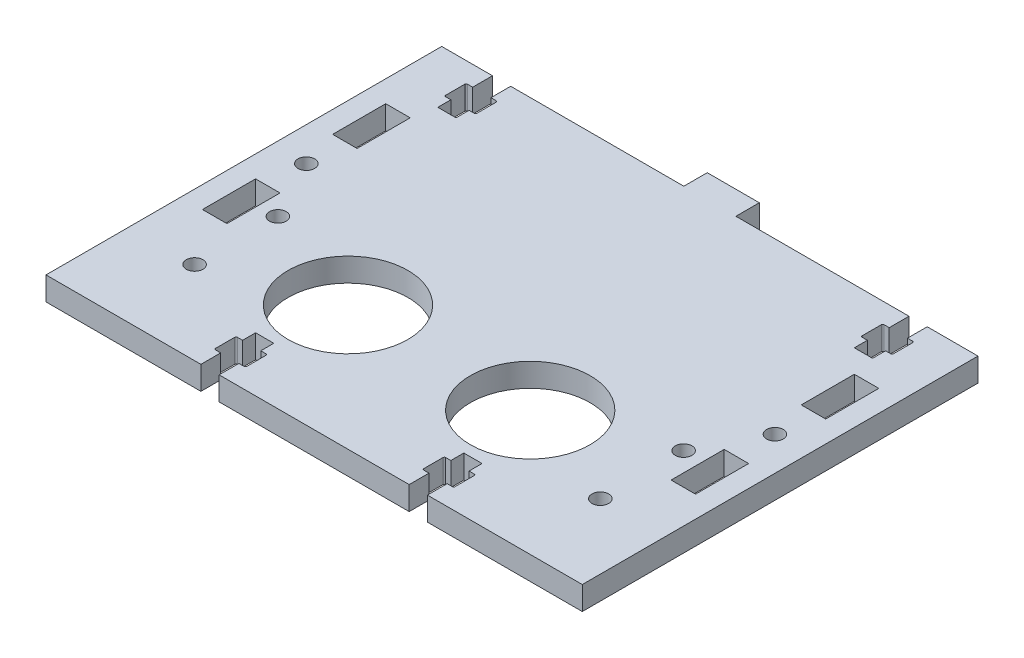
SolidWorks part; units mm, degrees
ref_plane "Front Plane" through (0, 0, 0) normal (0, 0, 1) x (1, 0, 0)
ref_plane "Top Plane" through (0, 0, 0) normal (0, 1, 0) x (1, 0, 0)
ref_plane "Right Plane" through (0, 0, 0) normal (1, 0, 0) x (0, 0, -1)
sketch "Sketch1" plane through (0, 0, 0) normal (0, 1, 0) x (1, 0, 0)
  line L1 (-51.5, 38) -> (51.5, 38)
  line L2 (-51.5, 38) -> (-51.5, -38)
  line L3 (-51.5, -38) -> (51.5, -38)
  line L4 (51.5, 38) -> (51.5, -38)
  line L5 (-51.5, 38) -> (51.5, -38) construction
  line L6 (-51.5, -38) -> (51.5, 38) construction
  point P0 (0, 0)
  dimension "D1" = 103
  dimension "D2" = 76
extrude "MainShape" add sketch "Sketch1" along normal blind 4.5
sketch "Sketch2" plane through (0, 4.5, 0) normal (0, 1, 0) x (1, 0, 0)
  line L0 (0, -38) -> (0, 38) construction
  line L1 (-51.5, -38) -> (51.5, -38) construction
  line L2 (51.5, 38) -> (-51.5, 38) construction
  line L4 (-5, 42.5) -> (5, 42.5)
  line L5 (-5, 42.5) -> (-5, 33.5)
  line L6 (-5, 33.5) -> (5, 33.5)
  line L7 (5, 42.5) -> (5, 33.5)
  line L8 (-5, 42.5) -> (5, 33.5) construction
  line L9 (-5, 33.5) -> (5, 42.5) construction
  dimension "D2" = 4.5
extrude "Tab1" add sketch "Sketch2" against normal through all
sketch "Sketch4" plane through (0, 4.5, 0) normal (0, 1, 0) x (1, 0, 0)
  line L0 (0, 42.5) -> (0, -38) construction
  line L1 (5, 42.5) -> (-5, 42.5) construction
  line L2 (-51.5, -38) -> (51.5, -38) construction
  line L3 (-40, 38) -> (-40, 27.5) construction
  line L4 (-5, 38) -> (-51.5, 38) construction
  line L5 (-38.25, 27.5) -> (-41.75, 27.5) construction
  line L6 (-41.75, 27.5) -> (-41.75, 38) construction
  line L7 (-38.25, 27.5) -> (-41.75, 27.5)
  line L8 (-41.75, 27.5) -> (-41.75, 30)
  line L9 (-41.75, 30) -> (-42.75, 30)
  line L10 (-43, 30.25) -> (-43, 33.95)
  line L11 (-42.75, 34.2) -> (-41.75, 34.2)
  line L12 (-41.75, 34.2) -> (-41.75, 38)
  line L13 (-41.75, 38) -> (-38.25, 38)
  line L14 (-38.25, 27.5) -> (-38.25, 38) construction
  line L15 (-38.25, 34.2) -> (-38.25, 38)
  line L16 (-37.25, 34.2) -> (-38.25, 34.2)
  line L17 (-37, 30.25) -> (-37, 33.95)
  line L18 (-38.25, 30) -> (-37.25, 30)
  line L19 (-38.25, 27.5) -> (-38.25, 30)
  line L20 (38.25, 27.5) -> (38.25, 38) construction
  line L21 (41.75, 27.5) -> (41.75, 38) construction
  line L22 (38.25, 27.5) -> (41.75, 27.5) construction
  line L23 (40, 38) -> (40, 27.5) construction
  line L24 (38.25, 27.5) -> (38.25, 30)
  line L25 (38.25, 30) -> (37.25, 30)
  line L26 (37, 30.25) -> (37, 33.95)
  line L27 (37.25, 34.2) -> (38.25, 34.2)
  line L28 (38.25, 34.2) -> (38.25, 38)
  line L29 (41.75, 38) -> (38.25, 38)
  line L30 (41.75, 34.2) -> (41.75, 38)
  line L31 (42.75, 34.2) -> (41.75, 34.2)
  line L32 (43, 30.25) -> (43, 33.95)
  line L33 (41.75, 30) -> (42.75, 30)
  line L34 (41.75, 27.5) -> (41.75, 30)
  line L35 (38.25, 27.5) -> (41.75, 27.5)
  arc A0 (-42.75, 30) -> (-43, 30.25) centre (-42.75, 30.25) cw
  arc A1 (-37, 30.25) -> (-37.25, 30) centre (-37.25, 30.25) cw
  arc A2 (-37.25, 34.2) -> (-37, 33.95) centre (-37.25, 33.95) cw
  arc A3 (-43, 33.95) -> (-42.75, 34.2) centre (-42.75, 33.95) cw
  arc A4 (43, 33.95) -> (42.75, 34.2) centre (42.75, 33.95) ccw
  arc A5 (37.25, 34.2) -> (37, 33.95) centre (37.25, 33.95) ccw
  arc A6 (37, 30.25) -> (37.25, 30) centre (37.25, 30.25) ccw
  arc A7 (42.75, 30) -> (43, 30.25) centre (42.75, 30.25) ccw
  point P24 (-43, 30)
  point P27 (-37, 30)
  point P30 (-37, 34.2)
  point P33 (-43, 34.2)
  point P56 (43, 34.2)
  point P57 (37, 34.2)
  point P58 (37, 30)
  point P59 (43, 30)
  dimension "D7" = 0.25
  dimension "D1" = 10.5
  dimension "D2" = 1.75
  dimension "D3" = 4.2
  dimension "D4" = 3
  dimension "D5" = 8
  dimension "D6" = 40
extrude "Cut-Extrude2" cut sketch "Sketch4" against normal through all
sketch "Sketch5" plane through (0, 4.5, 0) normal (0, 1, 0) x (1, 0, 0)
  line L0 (0, -38) -> (0, 42.5) construction
  line L1 (-51.5, -38) -> (51.5, -38) construction
  line L2 (5, 42.5) -> (-5, 42.5) construction
  line L3 (45, 38) -> (45, -38) construction
  line L4 (51.5, 38) -> (41.75, 38) construction
  line L5 (-45, 38) -> (-45, -38) construction
  line L6 (42.65, 23.1) -> (47.35, 23.1)
  line L7 (42.65, 23.1) -> (42.65, 12.9)
  line L8 (42.65, 12.9) -> (47.35, 12.9)
  line L9 (47.35, 23.1) -> (47.35, 12.9)
  line L10 (42.65, 23.1) -> (47.35, 12.9) construction
  line L11 (42.65, 12.9) -> (47.35, 23.1) construction
  line L12 (-42.65, 12.9) -> (-47.35, 23.1) construction
  line L13 (-42.65, 23.1) -> (-47.35, 12.9) construction
  line L14 (-47.35, 23.1) -> (-47.35, 12.9)
  line L15 (-42.65, 12.9) -> (-47.35, 12.9)
  line L16 (-42.65, 23.1) -> (-42.65, 12.9)
  line L17 (-42.65, 23.1) -> (-47.35, 23.1)
  line L18 (-51.5, 5.5) -> (51.5, 5.5) construction
  line L19 (-51.5, 38) -> (-51.5, -38) construction
  line L20 (51.5, -38) -> (51.5, 38) construction
  line L21 (-42.65, -12.1) -> (-47.35, -1.9) construction
  line L22 (-42.65, -1.9) -> (-47.35, -12.1) construction
  line L23 (42.65, -1.9) -> (47.35, -12.1) construction
  line L24 (42.65, -12.1) -> (47.35, -1.9) construction
  line L25 (-42.65, -12.1) -> (-47.35, -12.1)
  line L26 (-42.65, -12.1) -> (-42.65, -1.9)
  line L27 (-42.65, -1.9) -> (-47.35, -1.9)
  line L28 (-47.35, -12.1) -> (-47.35, -1.9)
  line L29 (47.35, -12.1) -> (47.35, -1.9)
  line L30 (42.65, -1.9) -> (47.35, -1.9)
  line L31 (42.65, -12.1) -> (42.65, -1.9)
  line L32 (42.65, -12.1) -> (47.35, -12.1)
  line L33 (-42.65, 23.1) -> (-47.35, 12.9) construction
  circle A0 centre (45, 5.5) radius 1.6
  circle A1 centre (-45, 5.5) radius 1.6
  point P10 (45, 18)
  point P21 (-45, 18)
  point P36 (-45, -7)
  point P37 (45, -7)
  dimension "D6" = 3.2
  dimension "D1" = 45
  dimension "D2" = 10.2
  dimension "D3" = 4.7
  dimension "D4" = 20
  dimension "D5" = 25
extrude "Cut-Extrude3" cut sketch "Sketch5" against normal through all
sketch "Sketch6" plane through (0, 4.5, 0) normal (0, 1, 0) x (1, 0, 0)
  line L0 (-17.5, -28) -> (-17.5, 28) construction
  line L2 (5, 42.5) -> (-5, 42.5) construction
  line L3 (-51.5, -14) -> (51.5, -14) construction
  line L4 (-51.5, 38) -> (-51.5, -38) construction
  line L5 (51.5, -38) -> (51.5, 38) construction
  line L6 (51.5, 38) -> (41.75, 38) construction
  line L7 (-51.5, -38) -> (51.5, -38) construction
  line L9 (-51.5, 38) -> (51.5, 38) construction
  circle A0 centre (-17.5, -14) radius 11.5
  point P4 (0, 42.5)
  dimension "D1" = 23
  dimension "D2" = 52
  dimension "D4" = 17.5
extrude "Cut-Extrude4" cut sketch "Sketch6" against normal through all
sketch "Sketch8" plane through (0, 4.5, 0) normal (0, 1, 0) x (1, 0, 0)
  line L0 (-17.5, -2.5) -> (-17.5, -25.5) construction
  line L1 (-17.5, -14) -> (-38.96, -14) construction
  line L2 (-38.96, -22) -> (-38.96, -6) construction
  line L3 (-17.5, -25.5) -> (-17.5, -2.5) construction
  circle A0 centre (-38.96, -6) radius 1.6
  circle A1 centre (-17.5, -14) radius 11.5 construction
  circle A2 centre (-38.96, -22) radius 1.6
  dimension "D3" = 3.2
  dimension "D1" = 0
  dimension "D4" = 21.46
extrude "Cut-Extrude6" cut sketch "Sketch8" against normal through all
sketch "Sketch9" plane through (0, 4.5, 0) normal (0, 1, 0) x (1, 0, 0)
  line L0 (0, -38) -> (0, 42.5) construction
  line L1 (-51.5, -38) -> (51.5, -38) construction
  line L2 (5, 42.5) -> (-5, 42.5) construction
  line L3 (20, -38) -> (20, -27.5) construction
  line L4 (18.25, -27.5) -> (21.75, -27.5) construction
  line L5 (21.75, -27.5) -> (21.75, -38) construction
  line L6 (21.75, -38) -> (21.75, -34.2)
  line L7 (21.75, -34.2) -> (22.75, -34.2)
  line L8 (23, -33.95) -> (23, -30.25)
  line L9 (22.75, -30) -> (21.75, -30)
  line L10 (21.75, -30) -> (21.75, -27.5)
  line L11 (21.75, -27.5) -> (18.25, -27.5)
  line L12 (21.75, -38) -> (18.25, -38)
  line L13 (18.25, -27.5) -> (18.25, -38) construction
  line L14 (18.25, -30) -> (18.25, -27.5)
  line L15 (17.25, -30) -> (18.25, -30)
  line L16 (17, -33.95) -> (17, -30.25)
  line L17 (18.25, -34.2) -> (17.25, -34.2)
  line L18 (18.25, -38) -> (18.25, -34.2)
  line L19 (-18.25, -27.5) -> (-18.25, -38) construction
  line L20 (-21.75, -27.5) -> (-21.75, -38) construction
  line L21 (-18.25, -27.5) -> (-21.75, -27.5) construction
  line L22 (-20, -38) -> (-20, -27.5) construction
  line L23 (-18.25, -38) -> (-18.25, -34.2)
  line L24 (-18.25, -34.2) -> (-17.25, -34.2)
  line L25 (-17, -33.95) -> (-17, -30.25)
  line L26 (-17.25, -30) -> (-18.25, -30)
  line L27 (-18.25, -30) -> (-18.25, -27.5)
  line L28 (-21.75, -38) -> (-18.25, -38)
  line L29 (-21.75, -27.5) -> (-18.25, -27.5)
  line L30 (-21.75, -30) -> (-21.75, -27.5)
  line L31 (-22.75, -30) -> (-21.75, -30)
  line L32 (-23, -33.95) -> (-23, -30.25)
  line L33 (-21.75, -34.2) -> (-22.75, -34.2)
  line L34 (-21.75, -38) -> (-21.75, -34.2)
  arc A0 (22.75, -34.2) -> (23, -33.95) centre (22.75, -33.95) ccw
  arc A1 (23, -30.25) -> (22.75, -30) centre (22.75, -30.25) ccw
  arc A2 (17, -30.25) -> (17.25, -30) centre (17.25, -30.25) cw
  arc A3 (17.25, -34.2) -> (17, -33.95) centre (17.25, -33.95) cw
  arc A4 (-17.25, -34.2) -> (-17, -33.95) centre (-17.25, -33.95) ccw
  arc A5 (-17, -30.25) -> (-17.25, -30) centre (-17.25, -30.25) ccw
  arc A6 (-23, -30.25) -> (-22.75, -30) centre (-22.75, -30.25) cw
  arc A7 (-22.75, -34.2) -> (-23, -33.95) centre (-22.75, -33.95) cw
  point P16 (23, -34.2)
  point P19 (23, -30)
  point P30 (17, -30)
  point P31 (17, -34.2)
  point P54 (-17, -34.2)
  point P55 (-17, -30)
  point P56 (-23, -30)
  point P57 (-23, -34.2)
  dimension "D7" = 0.25
  dimension "D1" = 10.5
  dimension "D2" = 1.75
  dimension "D3" = 8
  dimension "D4" = 4.2
  dimension "D5" = 3
  dimension "D6" = 20
extrude "Cut-Extrude7" cut sketch "Sketch9" against normal through all
sketch "Sketch10" [suppressed] plane through (0, 0, 28) normal (0, 0, 1) x (1, 0, 0)
  line L0 (-55, 2.25) -> (55, 2.25) construction
  line L1 (-55, 4.5) -> (-55, 0) construction
  line L2 (55, 4.5) -> (55, 0) construction
  line L3 (-16, 4.5) -> (-16, 0) construction
  line L4 (-14.25, 4.5) -> (-17.75, 4.5) construction
  line L5 (16, 4.5) -> (16, 0) construction
  line L6 (17.75, 4.5) -> (14.25, 4.5) construction
  line L7 (17.75, 0) -> (14.25, 0) construction
  line L8 (-14.25, 0) -> (-17.75, 0) construction
  circle A0 centre (-16, 2.25) radius 1.6
  circle A1 centre (16, 2.25) radius 1.6
  dimension "D1" = 3.2
  dimension "D2" = 3.2
mirror "Mirror1" about plane through (0, 0, 0) normal (1, 0, 0) of "Cut-Extrude6", "Cut-Extrude4"
equation "\"X-ROD-SPACING\"=45"
equation "\"Y-ROD-SPACING\"=75"
equation "\"Z-ROD-SPACING\"=17.5"
equation "\"Y-BED-OFFSET\"=2"
equation "\"Y-BED-ROD-INSET\"=3.5"
equation "\"Y-BED-SCREW-SPACING\"=209"
equation "\"Y-BED-SCREW-CUTOUT-SLOT-HEIGHT\"=1"
equation "\"T-SLOT-NUT-FILLET-RADIUS\"=0.25"
equation "\"T-SLOT-SCREW-SHAFT-RADIUS\"=1.75"
equation "\"T-SLOT-SCREW-SHAFT-CUTOUT-LENGTH\"=10.5"
equation "\"T-SLOT-NUT-DEPTH\"=4.2"
equation "\"T-SLOT-NUT-WIDTH\"=3"
equation "\"T-SLOT-NUT-END-DISTANCE\"=8"
equation "\"ACRYLIC-THICKNESS\"=10"
equation "\"ACRYLIC-THICKNESS2\"=4.5"
equation "\"ACRYLIC-TAB-CUTOUT-SIZE\"=\"ACRYLIC-THICKNESS\"+\"ACRYLIC-TAB-TOLERANCE\"*2"
equation "\"ACRYLIC-TAB-WIDTH\"=\"ACRYLIC-THICKNESS\""
equation "\"ACRYLIC-M3-HOLE\"=3.2"
equation "\"SMOOTHROD-CAP-SCREW-DISTANCE\"=20"
equation "\"FRAME-WIDTH-INNER\"=370"
equation "\"NEMA17-HOLE-SPACING\"=31"
equation "\"NEMA17-CENTRAL-CUTOUT\"=22.5"
equation "\"Z-BRACKET-REACH\"=55"
equation "\"Z-ROD-INSET\"=16"
equation "\"TOP-BRACKET-SPACING\"=40"
equation "\"SMOOTHROD-X-LENGTH\"=350"
equation "\"SMOOTHROD-Y-LENGTH\"=350"
equation "\"SMOOTHROD-Z-LENGTH\"=350"
equation "\"SMOOTHROD-TIGHTENING-HEADROOM\"=1"
equation "\"LEADSCREW-Z-LENGTH\"=300"
equation "\"SCREW-LENGTH-FRAME\"=\"ACRYLIC-THICKNESS\" + 10"
equation "\"SCREW-LENGTH-MOTOR\"=\"ACRYLIC-THICKNESS\" + 5"
equation "\"SCREW-LENGTH-EXTRUDER\"=28"
equation "\"SCREW-HEAD-RADIUS\"=6"
equation "\"PRINTED-X-SMOOTHROD-DIAMETER\"=8.2"
equation "\"PRINTED-X-SMOOTHROD-CUTOUT\"=10"
equation "\"PRINTED-X-BASE-HEIGHT\"=10"
equation "\"PRINTED-LM8UU-CUTOUT-SIZE\"=16"
equation "\"PRINTED-LM8UU-CUTOUT-LENGTH\"=24.5"
equation "\"PRINTED-X-IDLER-HEIGHT\"=16"
equation "\"PSU-MOUNTING-WIDTH\"=95"
equation "\"PSU-MOUNTING-HEIGHT\"=177"
equation "\"Y-BELT-TO-ROD-DISTANCE\"=20"
equation "\"SPOOL-HOLDER-ROD-SPACING\"=150"
equation "\"ACRYLIC-X-CARRIAGE-WIDTH\"=55"
equation "\"ACRYLIC-X-CARRIAGE-HEIGHT\"=75"
equation "\"ACRYLIC-X-CARRIAGE-SCREW-SPACING-X\"=15"
equation "\"ACRYLIC-X-CARRIAGE-SCREW-SPACING-Y\"=33"
equation "\"ACRYLIC-X-CARRIAGE-CENTER-TAB-SPACING\"=14"
equation "\"D1@MainShape\" = \"ACRYLIC-THICKNESS2\""
equation "\"D1@Sketch2\"=\"ACRYLIC-TAB-WIDTH\""
equation "\"D2@Sketch2\"=\"ACRYLIC-THICKNESS2\""
equation "\"D1@Sketch4\"=\"T-SLOT-SCREW-SHAFT-CUTOUT-LENGTH\""
equation "\"D2@Sketch4\"=\"T-SLOT-SCREW-SHAFT-RADIUS\""
equation "\"D3@Sketch4\"=\"T-SLOT-NUT-DEPTH\""
equation "\"D4@Sketch4\"=\"T-SLOT-NUT-WIDTH\""
equation "\"D5@Sketch4\"=\"T-SLOT-NUT-END-DISTANCE\""
equation "\"D7@Sketch4\"=\"T-SLOT-NUT-FILLET-RADIUS\""
equation "\"ACRYLIC-X-CARRIAGE-EXTRUDER-SHELF-DEPTH\"=\"ACRYLIC-X-CARRIAGE-EXTRUDER-OFFSET\" + 30"
equation "\"ACRYLIC-X-CARRIAGE-LM8UU-CUTOUT-WIDTH\"=24.25"
equation "\"ACRYLIC-X-CARRIAGE-EXTRUDER-BRACE-SPACING\"=23"
equation "\"ACRYLIC-X-CARRIAGE-EXTRUDER-BRACE-TAB-OFFSET\"=20"
equation "\"ACRYLIC-X-CARRIAGE-EXTRUDER-BRACE-HEIGHT\"=35"
equation "\"ACRYLIC-X-CARRIAGE-EXTRUDER-BRACE-SCREW-SPACING\"=22"
equation "\"D2@Sketch5\"=\"ACRYLIC-TAB-CUTOUT-SIZE\""
equation "\"D3@Sketch5\"=\"ACRYLIC-THICKNESS2\"+\"ACRYLIC-TAB-TOLERANCE\"*2"
equation "\"D4@Sketch5\"=\"ACRYLIC-X-CARRIAGE-EXTRUDER-BRACE-TAB-OFFSET\""
equation "\"D3@Sketch8\"=\"ACRYLIC-M3-HOLE\""
equation "\"ACRYLIC-X-CARRIAGE-EXTRUDER-ANGLE\"=90"
equation "\"ACRYLIC-X-CARRIAGE-EXTRUDER-OFFSET\"=26"
equation "\"D6@Sketch5\"=\"ACRYLIC-M3-HOLE\""
equation "\"D1@Sketch9\"=\"T-SLOT-SCREW-SHAFT-CUTOUT-LENGTH\""
equation "\"D2@Sketch9\"=\"T-SLOT-SCREW-SHAFT-RADIUS\""
equation "\"D3@Sketch9\"=\"T-SLOT-NUT-END-DISTANCE\""
equation "\"D4@Sketch9\"=\"T-SLOT-NUT-DEPTH\""
equation "\"D5@Sketch9\"=\"T-SLOT-NUT-WIDTH\""
equation "\"D7@Sketch9\"=\"T-SLOT-NUT-FILLET-RADIUS\""
equation "\"ACRYLIC-TAB-TOLERANCE\"=.1"
equation "\"ACRYLIC-X-CARRIAGE-DUAL-WIDTH-MULTIPLIER\"=1.65"
equation "\"ACRYLIC-X-CARRIAGE-DUAL-HOTEND-SPACING\"=42"
equation "\"ACRYLIC-X-CARRIAGE-DUAL-WIDTH\"=103"
equation "\"ACRYLIC-X-CARRIAGE-DUAL-HOTEND-SEPARATION\"=35"
equation "\"ACRYLIC-X-CARRIAGE-DUAL-MOUNT-PLATE-DEPTH\"=76"
equation "\"ACRYLIC-X-CARRIAGE-DUAL-MOUNT-BRACE-WIDTH\"=45"
equation "\"D1@Sketch5\"=\"ACRYLIC-X-CARRIAGE-DUAL-MOUNT-BRACE-WIDTH\""
equation "\"ACRYLIC-X-CARRIAGE-DUAL-MOUNT-SCREW-WIDTH\"=40"
equation "\"D6@Sketch4\"=\"ACRYLIC-X-CARRIAGE-DUAL-MOUNT-SCREW-WIDTH\""
equation "\"D1@Sketch1\"=\"ACRYLIC-X-CARRIAGE-DUAL-WIDTH\""
equation "\"D2@Sketch1\"=\"ACRYLIC-X-CARRIAGE-DUAL-MOUNT-PLATE-DEPTH\""
equation "\"D4@Sketch6\"=\"ACRYLIC-X-CARRIAGE-DUAL-HOTEND-SEPARATION\"/2"
